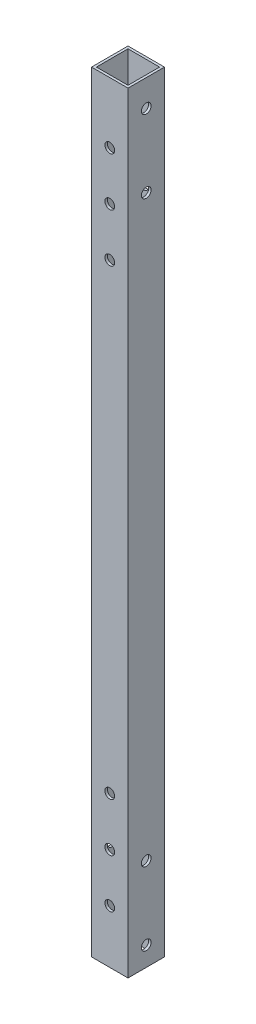
SolidWorks part; units mm, degrees
material "6061 合金"
ref_plane "Front" through (0, 0, 0) normal (0, 0, 1) x (1, 0, 0)
ref_plane "Top" through (0, 0, 0) normal (0, 1, 0) x (1, 0, 0)
ref_plane "Right" through (0, 0, 0) normal (1, 0, 0) x (0, 0, -1)
sketch "草图1" plane through (0, 0, 0) normal (0, 1, 0) x (1, 0, 0)
  line L1 (-7.5, -7.5) -> (7.5, -7.5)
  line L2 (-7.5, -7.5) -> (-7.5, 7.5)
  line L3 (-7.5, 7.5) -> (7.5, 7.5)
  line L4 (7.5, -7.5) -> (7.5, 7.5)
  line L5 (-7.5, -7.5) -> (7.5, 7.5) construction
  line L6 (-7.5, 7.5) -> (7.5, -7.5) construction
  line L7 (-6.5, -6.5) -> (6.5, -6.5)
  line L8 (-6.5, -6.5) -> (-6.5, 6.5)
  line L9 (-6.5, 6.5) -> (6.5, 6.5)
  line L10 (6.5, -6.5) -> (6.5, 6.5)
  line L11 (-6.5, -6.5) -> (6.5, 6.5) construction
  line L12 (-6.5, 6.5) -> (6.5, -6.5) construction
  point P0 (0, 0)
  point P5 (0, 0)
  dimension "D1" = 15
  dimension "D2" = 15
  dimension "D3" = 1
  dimension "D4" = 1
extrude "凸台-拉伸1" add sketch "草图1" along normal blind 320
sketch "草图3" plane through (0, 0, 7.5) normal (0, 0, 1) x (1, 0, 0)
  line L0 (0, 50) -> (0, -49950) construction
  line L1 (-7.5, 320) -> (7.5, 320) construction
  line L2 (5, 160) -> (-49995, 160) construction
  line L3 (7.5, 320) -> (7.5, 0) construction
  circle A0 centre (0, 295) radius 2
  circle A1 centre (0, 275) radius 2
  circle A2 centre (0, 45) radius 2
  circle A3 centre (0, 25) radius 2
  circle A4 centre (0, 255) radius 2
  circle A5 centre (0, 65) radius 2
  point P4 (0, 320)
  point P13 (7.5, 160)
  dimension "D1" = 4
  dimension "D2" = 4
  dimension "D5" = 4
  dimension "D3" = 20
  dimension "D4" = 25
  dimension "D6" = 20
extrude "切除-拉伸2" cut sketch "草图3" against normal through all
sketch "草图4" plane through (-7.5, 0, 0) normal (-1, 0, 0) x (0, 0, 1)
  line L0 (0, 0) -> (0, 50000) construction
  line L1 (-7.5, 0) -> (7.5, 0) construction
  line L2 (-7.5, 160) -> (49992.5, 160) construction
  line L3 (-7.5, 320) -> (-7.5, 0) construction
  line L4 (7.5, 320) -> (7.5, 0) construction
  circle A0 centre (0, 11) radius 2
  circle A1 centre (0, 41) radius 2
  circle A2 centre (0, 279) radius 2
  circle A3 centre (0, 309) radius 2
  point P13 (-7.5, 160)
  point P16 (7.5, 160)
  dimension "D1" = 4
  dimension "D2" = 4
  dimension "D3" = 11
  dimension "D4" = 30
extrude "切除-拉伸3" cut sketch "草图4" against normal through all
sketch "草图5" [suppressed] plane through (7.5, 0, 0) normal (1, 0, 0) x (0, 0, -1)
  circle A0 centre (0, 11) radius 2 construction
  circle A1 centre (0, 41) radius 2 construction
  circle A2 centre (0, 259) radius 2 construction
  circle A3 centre (0, 289) radius 2 construction
  circle A4 centre (0, 11) radius 2
  circle A5 centre (0, 41) radius 2
  circle A6 centre (0, 259) radius 2
  circle A7 centre (0, 289) radius 2
extrude "凸台-拉伸2" [suppressed] add sketch "草图5" against normal blind 1
ref_plane "基准面1" [suppressed] through (0, 0, 0) normal (-1, 0, 0) x (0, 0, 1)
mirror "镜向1" [suppressed] about plane through (0, 0, 0) normal (-1, 0, 0)
sketch "草图6" [suppressed] plane through (-7.5, 0, 0) normal (-1, 0, 0) x (0, 0, 1)
  line L0 (-7.5, 0) -> (7.5, 0) construction
  line L1 (7.5, 150) -> (-78.7867, 150) construction
  line L2 (7.5, 300) -> (7.5, 0) construction
  circle A0 centre (0, 16) radius 1.65
  circle A1 centre (0, 36) radius 1.65
  circle A2 centre (0, 284) radius 1.65
  circle A3 centre (0, 264) radius 1.65
  dimension "D1" = 20
  dimension "D2" = 16
  dimension "D3" = 3.3
extrude "切除-拉伸4" [suppressed] cut sketch "草图6" against normal through all
sketch "草图7" plane through (7.5, 0, 0) normal (1, 0, 0) x (0, 0, -1)
  line L0 (7.5, 320) -> (7.5, 0) construction
  line L1 (-7.5, 0) -> (7.5, 0)
  line L2 (-7.5, 0) -> (-7.5, 3)
  line L3 (-7.5, 3) -> (7.5, 3)
  line L4 (7.5, 0) -> (7.5, 3)
  dimension "D1" = 3
extrude "切除-拉伸6" cut sketch "草图7" against normal blind 20
equation "\"3。3\"=3.01309"
